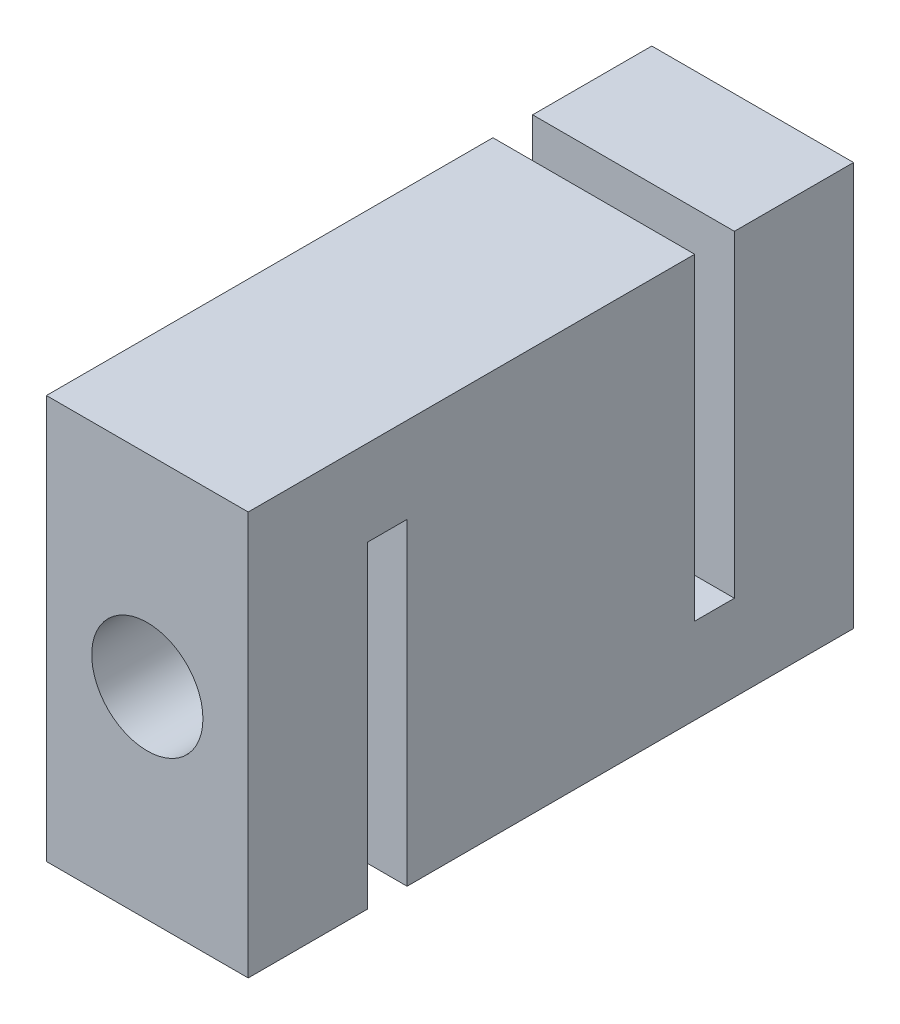
SolidWorks part; units mm, degrees
material "Plain Carbon Steel"
ref_plane "Front Plane" through (0, 0, 0) normal (0, 0, 1) x (1, 0, 0)
ref_plane "Top Plane" through (0, 0, 0) normal (0, 1, 0) x (1, 0, 0)
ref_plane "Right Plane" through (0, 0, 0) normal (1, 0, 0) x (0, 0, -1)
sketch "Sketch1" plane through (0, 0, 0) normal (0, 0, 1) x (1, 0, 0)
  line L1 (-15.0442, 30.1203) -> (10.3558, 30.1203)
  line L2 (-15.0442, 30.1203) -> (-15.0442, 80.9203)
  line L3 (-15.0442, 80.9203) -> (10.3558, 80.9203)
  line L4 (10.3558, 30.1203) -> (10.3558, 80.9203)
  dimension "D1" = 50.8
  dimension "D2" = 25.4
extrude "Boss-Extrude1" add sketch "Sketch1" along normal blind 76.2
sketch "Sketch2" plane through (-15.0442, 0, 0) normal (-1, 0, 0) x (0, 0, 1)
  line L0 (76.2, 80.9203) -> (0, 80.9203) construction
  line L1 (15, 80.9203) -> (20, 80.9203)
  line L2 (15, 80.9203) -> (15, 40.9203)
  line L3 (15, 40.9203) -> (20, 40.9203)
  line L4 (20, 80.9203) -> (20, 40.9203)
  line L5 (76.2, 30.1203) -> (0, 30.1203) construction
  line L6 (56.2, 30.1203) -> (61.2, 30.1203)
  line L7 (56.2, 30.1203) -> (56.2, 70.1203)
  line L8 (56.2, 70.1203) -> (61.2, 70.1203)
  line L9 (61.2, 30.1203) -> (61.2, 70.1203)
  line L10 (76.2, 80.9203) -> (76.2, 30.1203) construction
  line L11 (0, 80.9203) -> (0, 30.1203) construction
  dimension "D1" = 15
  dimension "D2" = 15
  dimension "D3" = 5
  dimension "D4" = 5
  dimension "D5" = 40
  dimension "D6" = 40
extrude "Cut-Extrude1" cut sketch "Sketch2" against normal through all
sketch "Sketch5" plane through (0, 0, 0) normal (0, 0, -1) x (-1, 0, 0)
  line L0 (-10.3558, 30.1203) -> (15.0442, 80.9203) construction
  point P6 (2.3442, 55.5203)
hole_wizard "Tap Drill for M16x2.0 Tap2" positions "Sketch5" profile "Sketch4" hole size "M16x2.0" standard "ANSI Metric" end condition up to next
sketch "Sketch4" plane through (-2.3442, 55.5203, 0) normal (1, 0, 0) x (0, 1, 0)
  line L0 (0, 0) -> (0, 15)
  line L1 (0, 15) -> (7, 15)
  line L2 (7, 15) -> (7, 0)
  line L5 (7, 0) -> (0, 0)
  line L11 (0, -6.35) -> (0, 107.95) construction
  dimension "Thru Hole Dia." = 14
  dimension "Thru Hole Depth" = 15
sketch "Sketch8" plane through (0, 0, 76.2) normal (0, 0, 1) x (1, 0, 0)
  line L0 (-15.0442, 30.1203) -> (10.3558, 80.9203) construction
  point P7 (-2.3442, 55.5203)
hole_wizard "Tap Drill for M16x2.0 Tap1" positions "Sketch8" profile "Sketch7" hole size "M16x2.0" standard "ANSI Metric" end condition up to next
sketch "Sketch7" plane through (-2.3442, 55.5203, 76.2) normal (1, 0, 0) x (0, -1, 0)
  line L0 (0, 0) -> (0, 15)
  line L1 (0, 15) -> (7, 15)
  line L2 (7, 15) -> (7, 0)
  line L5 (7, 0) -> (0, 0)
  line L11 (0, -6.35) -> (0, 107.95) construction
  dimension "Thru Hole Dia." = 14
  dimension "Thru Hole Depth" = 15
equation "\"D6@Sketch2\"=\"D5@Sketch2\""
equation "\"D3@Sketch2\"=\"D4@Sketch2\""
equation "\"D2@Sketch2\"=\"D1@Sketch2\""
